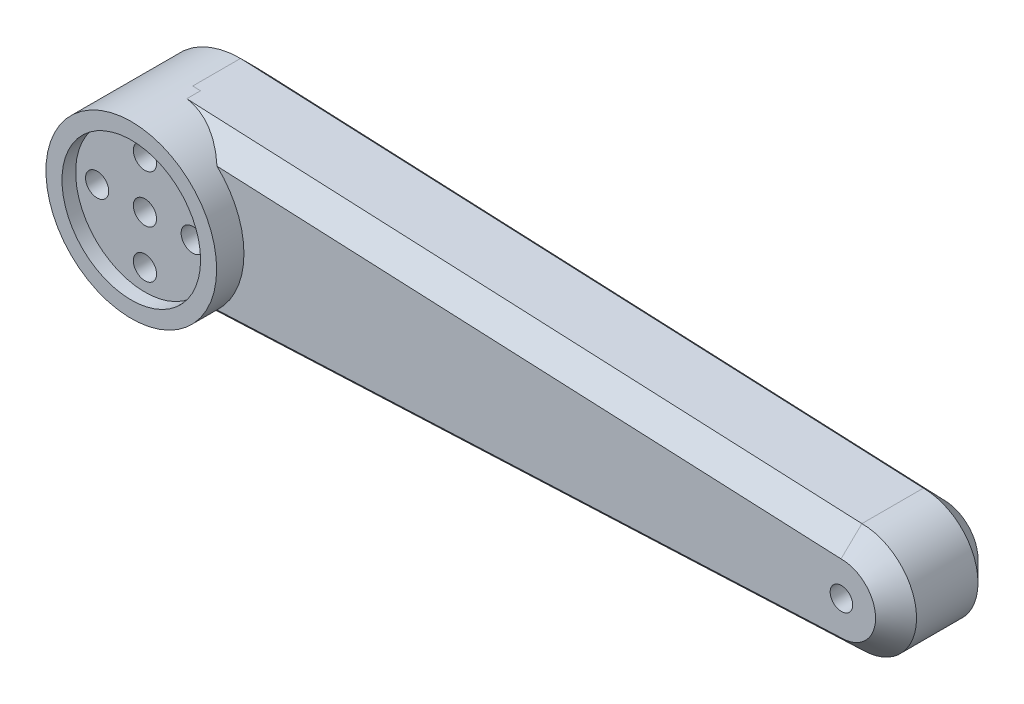
SolidWorks part; units mm, degrees
material "petg 20%"
ref_plane "Front Plane" through (0, 0, 0) normal (0, 0, 1) x (1, 0, 0)
ref_plane "Top Plane" through (0, 0, 0) normal (0, 1, 0) x (1, 0, 0)
ref_plane "Right Plane" through (0, 0, 0) normal (1, 0, 0) x (0, 0, -1)
sketch "Sketch1" plane through (0, 0, 0) normal (0, 0, 1) x (1, 0, 0)
  line L0 (0, 12.5) -> (100, 8)
  line L1 (0, -12.5) -> (100, -8)
  arc A0 (0, 12.5) -> (0, -12.5) centre (0, 0) ccw
  arc A1 (100, -8) -> (100, 8) centre (100, 0) ccw
  dimension "D1" = 25
  dimension "D2" = 16
  dimension "D3" = 100
extrude "Boss-Extrude1" add sketch "Sketch1" along normal blind 17
sketch "Sketch2" plane through (0, 0, 17) normal (0, 0, 1) x (1, 0, 0)
  circle A0 centre (0, 0) radius 12.5
  circle A1 centre (0, 0) radius 10.2
  dimension "D1" = 20.4
sketch "Sketch3" plane through (0, 0, 17) normal (0, 0, 1) x (1, 0, 0)
  circle A0 centre (0, 0) radius 1.7
  circle A1 centre (-7, 0) radius 1.7
  circle A2 centre (0, 7) radius 1.7
  circle A3 centre (7, 0) radius 1.7
  circle A4 centre (0, -7) radius 1.7
  point P14 (0, 0)
  dimension "D1" = 3.4
  dimension "D2" = 3.4
  dimension "D3" = 7
  dimension "D4" = 4
extrude "Cut-Extrude2" cut sketch "Sketch3" against normal through all
sketch "Sketch4" plane through (0, 0, 17) normal (0, 0, 1) x (1, 0, 0)
  circle A0 centre (100, 0) radius 1.65
  dimension "D1" = 3.3
extrude "Cut-Extrude3" cut sketch "Sketch4" against normal through all
sketch "Sketch5" plane through (0, 0, 0) normal (0, 0, -1) x (-1, 0, 0)
  circle A0 centre (0, 0) radius 3
  circle A1 centre (-7, 0) radius 3
  circle A2 centre (0, 7) radius 3
  circle A3 centre (7, 0) radius 3
  circle A4 centre (0, -7) radius 3
  point P15 (0, 0)
  dimension "D1" = 6
  dimension "D2" = 6
  dimension "D3" = 4
extrude "Cut-Extrude4" cut sketch "Sketch5" against normal blind 2
chamfer "Chamfer5" distance 3 angle 45 4 edges at (108, 0, 0) (50, -10.25, 0) (-12.5, 0, 0) (50, 10.25, 0)
extrude "Boss-Extrude4" add sketch "Sketch2" against normal blind 7 contours A0 | A1
sketch "Sketch6" plane through (0, 0, 17) normal (0, 0, 1) x (1, 0, 0)
  circle A0 centre (0, 7) radius 1.55
  circle A1 centre (7, 0) radius 1.55
  circle A2 centre (0, 0) radius 1.55
  circle A3 centre (0, -7) radius 1.55
  circle A4 centre (-7, 0) radius 1.55
  circle A5 centre (0, 0) radius 12.5
  circle A6 centre (0, 0) radius 10.15
sketch "Sketch7" plane through (0, 0, 17) normal (0, 0, 1) x (1, 0, 0)
  line L0 (100, 8) -> (0.8739, 12.4694)
  line L1 (0.8739, -12.4694) -> (100, -8)
  arc A0 (0.8739, -12.4694) -> (0.8739, 12.4694) centre (0, 0) ccw
  arc A1 (100, -8) -> (100, 8) centre (100, 0) ccw
extrude "Cut-Extrude5" cut sketch "Sketch7" against normal blind 2
chamfer "Chamfer6" distance 3 angle 45 3 edges at (50.5614, -10.2247, 15) (108, 0, 15) (50.5614, 10.2247, 15)
extrude "Boss-Extrude5" add sketch "Sketch6" along normal blind 2 contours A0 A5 A6 region at (-12.1464, 0, 17)
